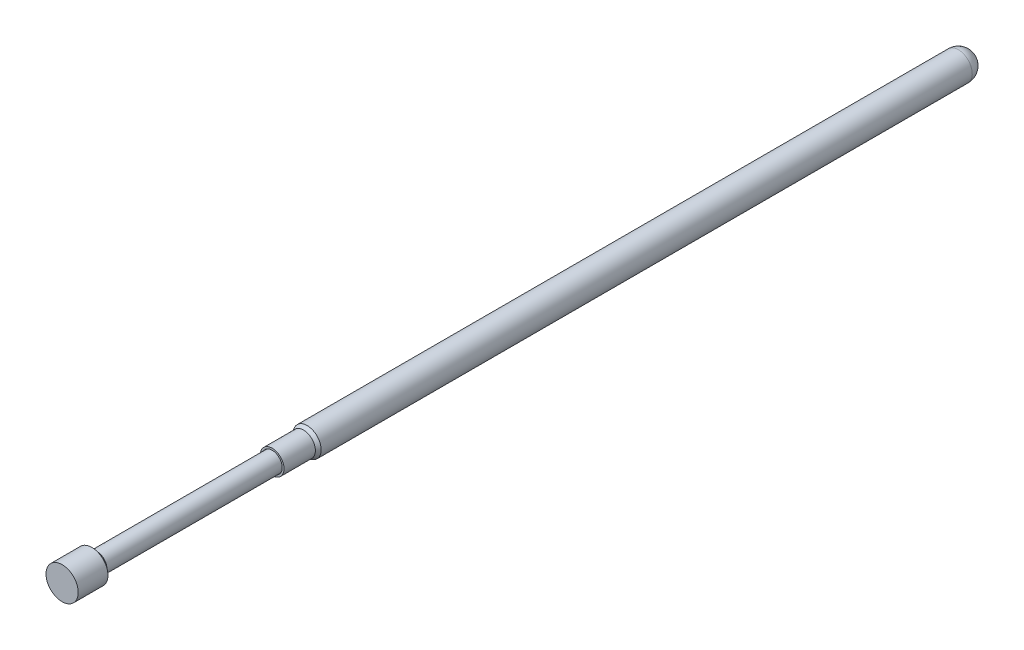
SolidWorks part; units mm, degrees
ref_plane "Front Plane" through (0, 0, 0) normal (0, 0, 1) x (1, 0, 0)
ref_plane "Top Plane" through (0, 0, 0) normal (0, 1, 0) x (1, 0, 0)
ref_plane "Right Plane" through (0, 0, 0) normal (1, 0, 0) x (0, 0, -1)
sketch "Sketch1" plane through (0, 0, 0) normal (1, 0, 0) x (0, 0, -1)
  line L0 (16.51, 0) -> (-16.51, 0) construction
  line L1 (-12.2682, 0.3556) -> (-12.2682, -0.3556) construction
  line L2 (16.51, -0.508) -> (16.51, 0.508) construction
  line L3 (-16.51, 0.5842) -> (-16.51, -0.5842) construction
  line L4 (-10.16, 0.3556) -> (-10.16, -0.3556) construction
  line L5 (3.81, 0) -> (3.81, 2.3549) construction
  line L6 (-8.89, 0.508) -> (-8.89, -0.508) construction
  point P0 (-8.89, 0)
  point P3 (-15.24, 0)
  point P4 (0, 0)
  point P8 (16.51, 0)
  point P11 (-16.51, 0)
  point P12 (-10.16, 0)
  point P13 (-12.2682, 0)
  point P17 (-10.16, 0)
  point P19 (12.7, 0)
  point P20 (-5.08, 0)
  point P25 (-12.2682, 0)
  point P26 (-8.89, 0)
  dimension "Overall Length" = 33.02
  dimension "Barrel Diameter" = 1.016
  dimension "Head Diameter" = 1.1684
  dimension "Barrel Length" = 25.4
  dimension "Compressed Length" = 26.67
  dimension "Working Stroke Length" = 4.2418
  dimension "Maximum Stroke Length" = 6.35
  dimension "Break View" = 17.78
  dimension "Head Length" = 1.27
  dimension "D1" = 0.7112
sketch "Sketch2" plane through (0, 0, 0) normal (1, 0, 0) x (0, 0, -1)
  line L0 (-8.89, 0) -> (16.51, 0) construction
  line L4 (-7.62, 0.508) -> (16.002, 0.508)
  line L7 (-8.89, 0) -> (-8.89, 0.4318)
  line L8 (-8.89, 0.4318) -> (-7.752, 0.4318)
  line L9 (-7.62, 0.508) -> (-7.752, 0.4318)
  line L10 (16.51, 0) -> (-8.89, 0)
  line L11 (16.002, 0) -> (16.002, 0.508) construction
  arc A2 (16.51, 0) -> (16.002, 0.508) centre (16.002, 0) ccw
  point P8 (-7.62, 0.508)
  point P13 (-7.752, 0.4318)
  point P17 (-7.752, 0.4318)
  point P21 (-7.62, 0.508)
  dimension "D6" = 1.016
  dimension "D2" = 0.8636
  dimension "D1" = 1.27
  dimension "D3" = 30
revolve "Revolve1" add sketch "Sketch2" angle 360 about L10
sketch "Sketch4" plane through (0, 0, 8.89) normal (0, 0, 1) x (1, 0, 0)
  circle A0 centre (0, 0) radius 0.3658
  dimension "D1" = 0.7315
extrude "Cut-Extrude1" cut sketch "Sketch4" against normal blind 13.335
sketch "Sketch3" plane through (0, 0, 0) normal (1, 0, 0) x (0, 0, -1)
  line L0 (-16.51, 0) -> (-16.51, 0.5842)
  line L1 (-16.51, 0.5842) -> (-16.51, -0.5842) construction
  line L2 (-16.51, 0.5842) -> (-15.4305, 0.5842)
  line L3 (-15.4305, 0.5842) -> (-15.24, 0.3556)
  line L4 (-15.24, 0.3556) -> (-8.89, 0.3556)
  line L5 (-8.89, 0.3556) -> (-8.89, 0)
  line L6 (-8.89, 0.4318) -> (-8.89, -0.4318) construction
  line L7 (-16.51, 0) -> (-8.89, 0)
  line L8 (16.51, 0) -> (-16.51, 0) construction
  line L9 (0, 0) -> (-8.89, 0) construction
  line L10 (-8.89, 0.3556) -> (-2.54, 0.3556)
  line L11 (-2.54, 0.3556) -> (-2.54, 0)
  line L12 (-2.54, 0) -> (-8.89, 0)
  point P10 (-15.24, 0.3556)
  dimension "D1" = 1.27
  dimension "D5" = 6.35
  dimension "D3" = 0.7112
  dimension "D2" = 1.0795
revolve "Revolve2" add sketch "Sketch3" angle 360 about L9 region at (0, 0.2039, 12.9905) region at (0, 0.1778, 5.715)
ref_axis "Center Axis 1" through (0, 0, 7.62) along (0, 0, -1)
ref_plane "Contact Plane 1" through (0, 0, 16.51) normal (0, 0, 1) x (1, 0, 0)
equation "\"D2@Sketch2\"=\"Barrel Diameter@Sketch1\"*0.85"
equation "\"D1@Sketch2\"=\"Head Length@Sketch1\""
equation "\"D6@Sketch2\"=\"Barrel Diameter@Sketch1\""
equation "\"D1@Sketch3\"=\"Head Length@Sketch1\""
equation "\"Break View@Sketch1\"=\"Barrel Length@Sketch1\" * .7"
equation "\"D1@Sketch4\"=\"Barrel Diameter@Sketch1\"*0.72"
equation "\"D1@Cut-Extrude1\"=\"Maximum Stroke Length@Sketch1\"*2.1"
equation "\"D3@Sketch3\"=\"Barrel Diameter@Sketch1\"*0.70"
equation "\"D2@Sketch3\"=\"D1@Sketch3\"*0.85"
equation "\"D5@Sketch3\"=\"Maximum Stroke Length@Sketch1\""
equation "\"D1@Sketch1\"=0.7*\"Barrel Diameter@Sketch1\""
